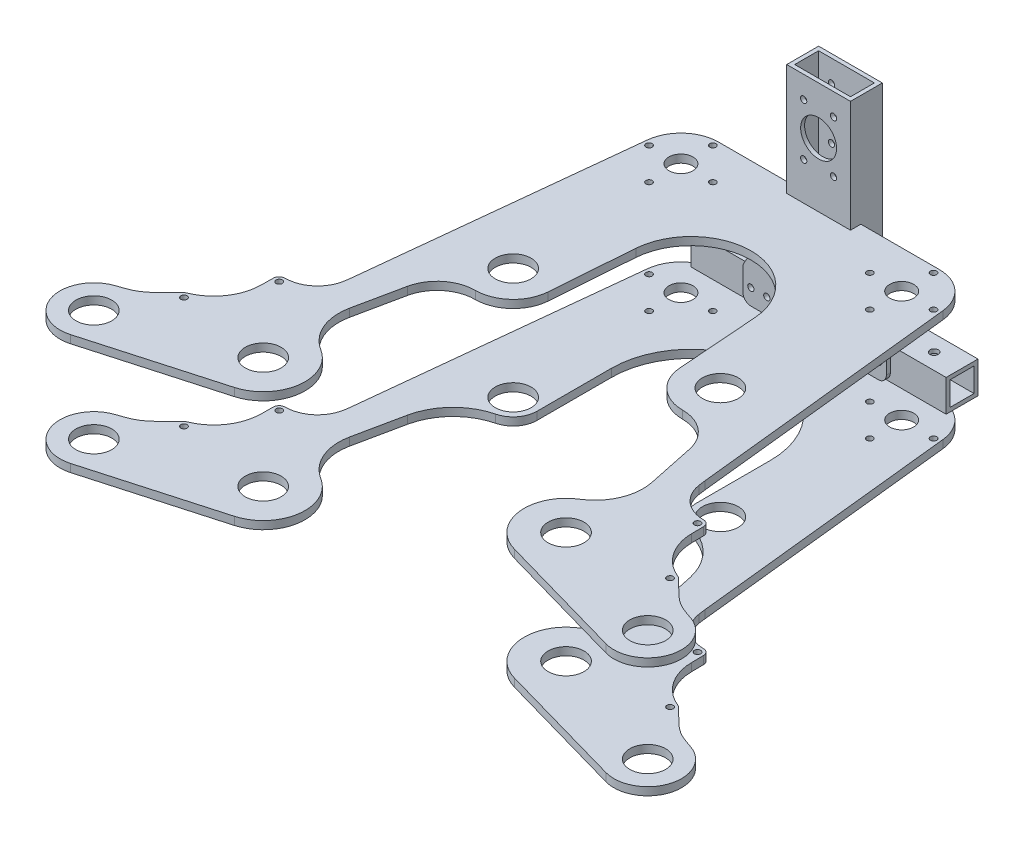
SolidWorks part; units mm, degrees
ref_plane "Alzado" through (0, 0, 0) normal (0, 0, 1) x (1, 0, 0)
ref_plane "Planta" through (0, 0, 0) normal (0, 1, 0) x (1, 0, 0)
ref_plane "Vista lateral" through (0, 0, 0) normal (1, 0, 0) x (0, 0, -1)
sketch "llantas" plane through (0, 0, 0) normal (0, 1, 0) x (1, 0, 0)
  line L0 (0, 221.5734) -> (0, 0) construction
  line L1 (-215.9, 0) -> (0, 0) construction
  circle A0 centre (-93.6625, 101.6) radius 50.8
  circle A1 centre (-215.9, 0) radius 38.1
  circle A2 centre (215.9, 0) radius 38.1
  circle A3 centre (93.6625, 101.6) radius 50.8
  dimension "D1" = 101.6
  dimension "D2" = 42.8625
  dimension "D3" = 177.8
  dimension "D4" = 76.2
  dimension "D5" = 101.6
sketch "cono" plane through (0, 0, 0) normal (1, 0, 0) x (0, 0, -1)
  line L0 (-76.2, 23.114) -> (-22.987, 324.358)
  line L1 (-22.987, 324.358) -> (22.987, 324.358)
  line L2 (0, 324.358) -> (0, 23.114) construction
  line L3 (76.2, 23.114) -> (-76.2, 23.114) construction
  line L4 (-76.2, 23.114) -> (-106.426, 23.114)
  line L5 (-106.426, 23.114) -> (-106.426, 0)
  line L6 (-106.426, 0) -> (106.426, 0)
  line L7 (0, 0) -> (0, 23.114)
  line L8 (-76.2, 23.114) -> (76.2, 23.114)
  line L9 (-80.283, 0) -> (80.283, 0)
  line L10 (221.5734, 0) -> (0, 0) construction
  line L11 (106.426, 23.114) -> (106.426, 0)
  line L12 (76.2, 23.114) -> (106.426, 23.114)
  line L13 (76.2, 23.114) -> (22.987, 324.358)
  line L14 (0, 220.8278) -> (41.275, 220.8278) construction
  dimension "D1" = 324.358
  dimension "D2" = 23.114
  dimension "D3" = 22.987
  dimension "D4" = 152.4
  dimension "D5" = 212.852
  dimension "D6" = 41.275
  dimension "D7" = 220.8278
sketch "Croquis4" plane through (0, 0, 0) normal (0, 1, 0) x (1, 0, 0)
  line L11 (0, 293.4478) -> (0, -300.8756) construction
  circle A36 centre (0, 179.087) radius 32.258
  dimension "D4" = 64.516
ref_plane "Plano1" through (0, 184.15, 0) normal (0, 1, 0) x (1, 0, 0)
sketch "Croquis11" plane through (0, 184.15, 0) normal (0, 1, 0) x (1, 0, 0)
  line L0 (0, -106.426) -> (0, 106.426) construction
  line L1 (-97.4367, 80.798) -> (-111.0577, -56.3986) construction
  line L2 (0, 0) -> (0, -47.7539) construction
  line L3 (-78.5329, 81.5298) -> (-54.3464, -54.2032) construction
  line L4 (-102.0644, -224.6803) -> (-63.9644, -63.6256) construction
  line L5 (-139.2356, -215.8869) -> (-101.1356, -54.8321) construction
  line L6 (0, 0) -> (-82.55, -59.2289) construction
  line L7 (0, 0) -> (0, -106.426) construction
  line L14 (-126.947, -202.253) -> (-226.9506, -237.178) construction
  line L15 (-114.353, -238.3143) -> (-214.3566, -273.2393) construction
  line L16 (0, 293.4478) -> (0, -300.8756) construction
  line L17 (-220.6536, -283.7836) -> (-120.65, -283.7836) construction
  circle A0 centre (0, 0) radius 47.7539 construction
  circle A1 centre (-82.55, -59.2289) radius 50.8
  circle A2 centre (-87.9341, 79.8546) radius 30
  arc A3 (-78.5329, 81.5298) -> (-97.4367, 80.798) centre (-87.9341, 79.8546) ccw construction
  arc A4 (-111.0577, -56.3986) -> (-54.3464, -54.2032) centre (-82.55, -59.2289) ccw construction
  arc A6 (-139.2356, -215.8869) -> (-102.0644, -224.6803) centre (-120.65, -220.2836) ccw construction
  arc A7 (-63.9644, -63.6256) -> (-101.1356, -54.8321) centre (-82.55, -59.2289) ccw construction
  circle A12 centre (-120.65, -220.2836) radius 50.8
  circle A13 centre (-220.6536, -255.2086) radius 28.575
  arc A14 (-226.9506, -237.178) -> (-214.3566, -273.2393) centre (-220.6536, -255.2086) ccw construction
  arc A15 (-114.353, -238.3143) -> (-139.2356, -215.8869) centre (-120.65, -220.2836) ccw construction
  point P19 (0, 0)
  dimension "D1" = 101.6
  dimension "D4" = 60
  dimension "D5" = 19.0986
  dimension "D6" = 57.2958
  dimension "D10" = 38.1972
  dimension "D17" = 101.6
  dimension "D13" = 57.15
  dimension "D14" = 38.1972
  dimension "D2" = 101.6
  dimension "D3" = 165.1
  dimension "D8" = 69.85
  dimension "D9" = 12.7
sketch "Croquis40" plane through (0, 184.15, 0) normal (0, 1, 0) x (1, 0, 0)
  line L0 (-117.475, -110.0289) -> (117.475, -110.0289) construction
  line L1 (-117.475, -110.0289) -> (-117.475, -344.9789) construction
  line L2 (117.475, -110.0289) -> (117.475, -344.9789) construction
  line L3 (-117.475, -344.9789) -> (117.475, -344.9789) construction
  line L4 (0, 0) -> (0, -110.0289)
  circle A1 centre (-82.55, -59.2289) radius 50.8 construction
  dimension "D1" = 234.95
ref_plane "Plano2" through (0, 95.25, 0) normal (0, 1, 0) x (1, 0, 0)
sketch "Croquis12" plane through (0, 95.25, 0) normal (0, 1, 0) x (1, 0, 0)
  line L0 (0, 0) -> (0, -63.4576) construction
  circle A0 centre (0, 0) radius 63.4576 construction
  circle A1 centre (-82.55, -59.2289) radius 50.8
  circle A2 centre (-82.55, -59.2289) radius 50.8 construction
sketch "Croquis42" plane through (0, 184.15, 0) normal (0, 1, 0) x (1, 0, 0)
  line L10 (140.3668, -129.3051) -> (117.7656, 83.0299)
  line L11 (-47.6217, 3.5515) -> (-52.471, -61.4721)
  line L12 (-112.3836, -113.6275) -> (-120.3575, -151.7275)
  line L13 (-120.65, -220.2836) -> (-220.6536, -255.2086) construction
  line L14 (-111.5648, -252.3593) -> (-213.299, -281.1746)
  line L15 (0, 226.6032) -> (0, -226.6032) construction
  line L17 (229.5516, -229.7302) -> (216.339, -225.1159)
  line L18 (-229.5516, -229.7302) -> (-216.339, -225.1159)
  line L19 (-140.3668, -129.3051) -> (-117.7656, 83.0299)
  line L20 (-126.947, -202.253) -> (-226.9506, -237.178) construction
  line L21 (-87.9341, 109.8546) -> (87.9341, 109.8546)
  line L22 (111.5648, -252.3593) -> (213.299, -281.1746)
  line L23 (112.3836, -113.6275) -> (120.3575, -151.7275)
  line L24 (47.6217, 3.5515) -> (52.471, -61.4721)
  circle A11 centre (-220.6536, -255.2086) radius 14.2875
  circle A17 centre (-120.65, -220.2836) radius 14.2875
  circle A18 centre (-82.55, -59.2289) radius 14.2875
  arc A20 (47.6217, 3.5515) -> (-47.6217, 3.5515) centre (0, 0) ccw
  circle A21 centre (87.9341, 79.8546) radius 25.4 construction
  circle A22 centre (0, 0) radius 47.7539 construction
  arc A23 (-82.55, -89.3914) -> (-52.471, -61.4721) centre (-82.55, -59.2289) ccw
  arc A24 (-82.55, -89.3914) -> (-112.3836, -113.6275) centre (-82.55, -119.8714) ccw
  arc A25 (-111.5648, -252.3593) -> (-103.1106, -191.933) centre (-120.65, -220.2836) ccw
  arc A26 (-120.3575, -151.7275) -> (-103.1106, -191.933) centre (-83.0655, -159.5323) ccw
  arc A28 (-229.5516, -229.7302) -> (-213.299, -281.1746) centre (-220.6536, -255.2086) ccw
  circle A29 centre (120.65, -220.2836) radius 33.3375 construction
  circle A30 centre (113.3341, 79.8546) radius 2.4892
  circle A31 centre (-87.9341, 79.8546) radius 30 construction
  arc A32 (-87.9341, 109.8546) -> (-117.7656, 83.0299) centre (-87.9341, 79.8546) ccw
  circle A33 centre (-120.65, -220.2836) radius 33.3375 construction
  circle A34 centre (-87.9341, 79.8546) radius 25.4 construction
  circle A35 centre (-87.9341, 105.2546) radius 2.4892
  circle A36 centre (-62.5341, 79.8546) radius 2.4892
  circle A37 centre (-87.9341, 54.4546) radius 2.4892
  circle A38 centre (-113.3341, 79.8546) radius 2.4892
  circle A39 centre (87.9341, 54.4546) radius 2.4892
  circle A40 centre (62.5341, 79.8546) radius 2.4892
  circle A41 centre (87.9341, 105.2546) radius 2.4892
  arc A42 (87.9341, 109.8546) -> (117.7656, 83.0299) centre (87.9341, 79.8546) cw
  arc A43 (229.5516, -229.7302) -> (213.299, -281.1746) centre (220.6536, -255.2086) cw
  arc A44 (120.3575, -151.7275) -> (103.1106, -191.933) centre (83.0655, -159.5323) cw
  arc A45 (111.5648, -252.3593) -> (103.1106, -191.933) centre (120.65, -220.2836) cw
  arc A46 (82.55, -89.3914) -> (112.3836, -113.6275) centre (82.55, -119.8714) cw
  arc A47 (82.55, -89.3914) -> (52.471, -61.4721) centre (82.55, -59.2289) cw
  circle A48 centre (82.55, -59.2289) radius 14.2875
  circle A49 centre (120.65, -220.2836) radius 14.2875
  circle A50 centre (220.6536, -255.2086) radius 14.2875
  arc A52 (140.3668, -129.3051) -> (216.339, -225.1159) centre (254.0248, -117.2072) ccw
  arc A53 (-216.339, -225.1159) -> (-140.3668, -129.3051) centre (-254.0248, -117.2072) ccw
  circle A54 centre (-87.9341, 79.8546) radius 9.5631
  circle A55 centre (87.9341, 79.8546) radius 9.5631
  point P18 (-170.6518, -237.7461)
  point P52 (-87.9341, 79.8546)
  point P66 (148.0256, -201.2583)
  point P83 (0, 109.8546)
  point P85 (87.9341, 79.8546)
  point P86 (170.6518, -237.7461)
  point P90 (-148.0256, -201.2583)
  dimension "D1" = 28.575
  dimension "D2" = 19.05
  dimension "D3" = 12.7
  dimension "D4" = 15.875
  dimension "D5" = 38.1
  dimension "D7" = 30.48
  dimension "D8" = 50.8
  dimension "D9" = 4.9784
  dimension "D11" = 114.3
  dimension "D12" = 19.1262
  dimension "D6" = 38.1
  dimension "D10" = 4
extrude "4400-23-P-0501" add sketch "Croquis42" along normal blind 6.35
sketch "Croquis44" plane through (0, 95.25, 0) normal (0, 1, 0) x (1, 0, 0)
  line L0 (87.9341, 109.8546) -> (-87.9341, 109.8546) construction
  line L1 (-117.7656, 83.0299) -> (-140.3668, -129.3051) construction
  line L2 (87.9341, 109.8546) -> (-87.9341, 109.8546)
  line L3 (-117.7656, 83.0299) -> (-140.3668, -129.3051)
  line L4 (140.3668, -129.3051) -> (117.7656, 83.0299) construction
  line L5 (229.5516, -229.7302) -> (216.339, -225.1159) construction
  line L6 (111.5648, -252.3593) -> (213.299, -281.1746) construction
  line L7 (112.3836, -113.6275) -> (120.3575, -151.7275) construction
  line L10 (-120.3575, -151.7275) -> (-112.3836, -113.6275) construction
  line L11 (-213.299, -281.1746) -> (-111.5648, -252.3593) construction
  line L12 (-216.339, -225.1159) -> (-229.5516, -229.7302) construction
  line L13 (140.3668, -129.3051) -> (117.7656, 83.0299)
  line L14 (229.5516, -229.7302) -> (216.339, -225.1159)
  line L15 (111.5648, -252.3593) -> (213.299, -281.1746)
  line L16 (112.3836, -113.6275) -> (120.3575, -151.7275)
  line L19 (-120.3575, -151.7275) -> (-112.3836, -113.6275)
  line L20 (-213.299, -281.1746) -> (-111.5648, -252.3593)
  line L21 (-216.339, -225.1159) -> (-229.5516, -229.7302)
  line L22 (-63.4576, -59.2289) -> (-63.4576, 0)
  line L23 (63.4576, -59.2289) -> (63.4576, 0)
  line L24 (0, 0) -> (0, -147.841) construction
  arc A0 (-216.339, -225.1159) -> (-140.3668, -129.3051) centre (-254.0248, -117.2072) ccw construction
  arc A1 (-87.9341, 109.8546) -> (-117.7656, 83.0299) centre (-87.9341, 79.8546) ccw construction
  arc A2 (-216.339, -225.1159) -> (-140.3668, -129.3051) centre (-254.0248, -117.2072) ccw
  arc A3 (-87.9341, 109.8546) -> (-117.7656, 83.0299) centre (-87.9341, 79.8546) ccw
  arc A4 (117.7656, 83.0299) -> (87.9341, 109.8546) centre (87.9341, 79.8546) ccw construction
  arc A5 (140.3668, -129.3051) -> (216.339, -225.1159) centre (254.0248, -117.2072) ccw construction
  arc A6 (213.299, -281.1746) -> (229.5516, -229.7302) centre (220.6536, -255.2086) ccw construction
  arc A7 (103.1106, -191.933) -> (111.5648, -252.3593) centre (120.65, -220.2836) ccw construction
  arc A8 (103.1106, -191.933) -> (120.3575, -151.7275) centre (83.0655, -159.5323) ccw construction
  arc A14 (-120.3575, -151.7275) -> (-103.1106, -191.933) centre (-83.0655, -159.5323) ccw construction
  arc A15 (-111.5648, -252.3593) -> (-103.1106, -191.933) centre (-120.65, -220.2836) ccw construction
  arc A16 (-229.5516, -229.7302) -> (-213.299, -281.1746) centre (-220.6536, -255.2086) ccw construction
  arc A17 (117.7656, 83.0299) -> (87.9341, 109.8546) centre (87.9341, 79.8546) ccw
  arc A18 (140.3668, -129.3051) -> (216.339, -225.1159) centre (254.0248, -117.2072) ccw
  arc A19 (213.299, -281.1746) -> (229.5516, -229.7302) centre (220.6536, -255.2086) ccw
  arc A20 (103.1106, -191.933) -> (111.5648, -252.3593) centre (120.65, -220.2836) ccw
  arc A21 (103.1106, -191.933) -> (120.3575, -151.7275) centre (83.0655, -159.5323) ccw
  arc A27 (-120.3575, -151.7275) -> (-103.1106, -191.933) centre (-83.0655, -159.5323) ccw
  arc A28 (-111.5648, -252.3593) -> (-103.1106, -191.933) centre (-120.65, -220.2836) ccw
  arc A29 (-229.5516, -229.7302) -> (-213.299, -281.1746) centre (-220.6536, -255.2086) ccw
  circle A30 centre (87.9341, 79.8546) radius 9.5631 construction
  circle A31 centre (87.9341, 54.4546) radius 2.4892 construction
  circle A32 centre (113.3341, 79.8546) radius 2.4892 construction
  circle A33 centre (87.9341, 105.2546) radius 2.4892 construction
  circle A34 centre (62.5341, 79.8546) radius 2.4892 construction
  circle A35 centre (-87.9341, 79.8546) radius 9.5631 construction
  circle A36 centre (-62.5341, 79.8546) radius 2.4892 construction
  circle A37 centre (-87.9341, 105.2546) radius 2.4892 construction
  circle A38 centre (-113.3341, 79.8546) radius 2.4892 construction
  circle A39 centre (-87.9341, 54.4546) radius 2.4892 construction
  circle A40 centre (220.6536, -255.2086) radius 14.2875 construction
  circle A41 centre (120.65, -220.2836) radius 14.2875 construction
  circle A42 centre (82.55, -59.2289) radius 14.2875 construction
  circle A43 centre (-82.55, -59.2289) radius 14.2875 construction
  circle A44 centre (-120.65, -220.2836) radius 14.2875 construction
  circle A45 centre (-220.6536, -255.2086) radius 14.2875 construction
  circle A46 centre (87.9341, 79.8546) radius 9.5631
  circle A47 centre (87.9341, 54.4546) radius 2.4892
  circle A48 centre (113.3341, 79.8546) radius 2.4892
  circle A49 centre (87.9341, 105.2546) radius 2.4892
  circle A50 centre (62.5341, 79.8546) radius 2.4892
  circle A51 centre (-87.9341, 79.8546) radius 9.5631
  circle A52 centre (-62.5341, 79.8546) radius 2.4892
  circle A53 centre (-87.9341, 105.2546) radius 2.4892
  circle A54 centre (-113.3341, 79.8546) radius 2.4892
  circle A55 centre (-87.9341, 54.4546) radius 2.4892
  circle A56 centre (220.6536, -255.2086) radius 14.2875
  circle A57 centre (120.65, -220.2836) radius 14.2875
  circle A58 centre (82.55, -59.2289) radius 14.2875
  circle A59 centre (-82.55, -59.2289) radius 14.2875
  circle A60 centre (-120.65, -220.2836) radius 14.2875
  circle A61 centre (-220.6536, -255.2086) radius 14.2875
  arc A62 (63.4576, 0) -> (-63.4576, 0) centre (0, 0) ccw
  arc A64 (-63.4576, -59.2289) -> (-77.9, -77.7463) centre (-82.55, -59.2289) cw
  arc A65 (-112.3836, -113.6275) -> (-77.9, -77.7463) centre (-66.477, -123.2353) cw
  circle A66 centre (0, 0) radius 63.4576 construction
  arc A67 (112.3836, -113.6275) -> (77.9, -77.7463) centre (66.477, -123.2353) ccw
  arc A68 (63.4576, -59.2289) -> (77.9, -77.7463) centre (82.55, -59.2289) ccw
extrude "4400-23-P-0502" add sketch "Croquis44" along normal blind 6.35
sketch "Croquis45" plane through (0, 95.25, 0) normal (0, -1, 0) x (1, 0, 0)
  line L7 (-126.947, 202.253) -> (-226.9506, 237.178) construction
  circle A0 centre (-189.6273, 213.7178) radius 4.7625 construction
  circle A1 centre (-189.6273, 213.7178) radius 2.4892
  circle A6 centre (-220.6536, 255.2086) radius 38.1
  circle A7 centre (-220.6536, 255.2086) radius 38.1 construction
  circle A9 centre (-120.65, 220.2836) radius 63.5
  circle A10 centre (-120.65, 220.2836) radius 63.5 construction
  dimension "D1" = 9.525
  dimension "D2" = 4.9784
  dimension "D5" = 5.08
  dimension "D3" = 9.525
  dimension "D4" = 12.7
sketch "Croquis46" plane through (0, 190.5, 0) normal (0, 1, 0) x (1, 0, 0)
  line L0 (-184.6841, -242.6467) -> (-180.5992, -241.2201) construction
  line L1 (-126.947, -202.253) -> (-226.9506, -237.178) construction
  line L2 (-220.6536, -255.2086) -> (-120.65, -220.2836) construction
  line L3 (-182.6417, -241.9334) -> (-193.6494, -210.4142) construction
  line L4 (-166.6601, -156.7836) -> (-120.65, -156.7836) construction
  line L5 (-215.1814, -224.7046) -> (-196.9691, -206.9994)
  line L6 (-171.8045, -196.6069) -> (-195.4084, -205.9885)
  line L7 (-171.8045, -196.6069) -> (-171.4223, -161.4943)
  line L8 (0, 0) -> (0, -195.4432) construction
  line L9 (166.6601, -156.7836) -> (120.65, -156.7836) construction
  line L10 (182.6417, -241.9334) -> (193.6494, -210.4142) construction
  line L11 (220.6536, -255.2086) -> (120.65, -220.2836) construction
  line L12 (184.6841, -242.6467) -> (180.5992, -241.2201) construction
  line L13 (171.8045, -196.6069) -> (171.4223, -161.4943)
  line L14 (171.8045, -196.6069) -> (195.4084, -205.9885)
  line L15 (215.1814, -224.7046) -> (196.9691, -206.9994)
  circle A0 centre (-220.6536, -255.2086) radius 38.1 construction
  circle A1 centre (-193.6494, -210.4142) radius 4.7625 construction
  circle A2 centre (-193.6494, -210.4142) radius 2.4892
  circle A3 centre (-166.6601, -161.5461) radius 4.7625 construction
  circle A4 centre (-166.6601, -161.5461) radius 2.4892
  arc A5 (-216.339, -225.1159) -> (-140.3668, -129.3051) centre (-254.0248, -117.2072) ccw construction
  circle A6 centre (-120.65, -220.2836) radius 63.5 construction
  arc A7 (-196.9691, -206.9994) -> (-195.4084, -205.9885) centre (-193.6494, -210.4142) cw
  arc A8 (-171.4223, -161.4943) -> (-166.6601, -156.7836) centre (-166.6601, -161.5461) cw
  arc A9 (-166.6601, -156.7836) -> (-141.1068, -134.9277) centre (-166.6601, -130.9175) ccw
  arc A10 (-215.1814, -224.7046) -> (-141.1068, -134.9277) centre (-254.0248, -117.2072) ccw
  circle A11 centre (166.6601, -161.5461) radius 4.7625 construction
  circle A12 centre (193.6494, -210.4142) radius 4.7625 construction
  arc A13 (215.1814, -224.7046) -> (141.1068, -134.9277) centre (254.0248, -117.2072) cw
  arc A14 (166.6601, -156.7836) -> (141.1068, -134.9277) centre (166.6601, -130.9175) cw
  arc A15 (171.4223, -161.4943) -> (166.6601, -156.7836) centre (166.6601, -161.5461) ccw
  arc A16 (196.9691, -206.9994) -> (195.4084, -205.9885) centre (193.6494, -210.4142) ccw
  circle A17 centre (166.6601, -161.5461) radius 2.4892
  circle A18 centre (193.6494, -210.4142) radius 2.4892
  point P20 (-182.6417, -241.9334)
  arc M29 (216.339, -225.1159) -> (140.3668, -129.3051) centre (254.0248, -117.2072) cw
  arc M35 (-140.3668, -129.3051) -> (-216.339, -225.1159) centre (-254.0248, -117.2072) cw
  dimension "D1" = 4.9784
  dimension "D2" = 9.525
  dimension "D4" = 6.35
  dimension "D3" = 9.525
  dimension "D5" = 25.4
extrude "Saliente-Extruir2" add sketch "Croquis46" against normal up to surface (6.35 mm away) contours A9 A8 L7 A4 M35 | A7 L5 A2 L6 M35 | L13 A15 A14 A17 M29 | A18 L15 A16 L14 M29 region at (-160.7365, 190.5, 168.9261) region at (-205.715, 190.5, 216.2225) region at (160.7365, 190.5, 168.9261) region at (183.4155, 190.5, 201.778) up to face at (0, 184.15, 117.4282)
fillet "Redondeo1" radius 38.1 2 edges at (-215.1814, 187.325, 224.7046) (-171.8045, 187.325, 196.6069)
extrude "Saliente-Extruir3" add sketch "Croquis46<3>" against normal up to surface (95.25 mm away) from surface contours A9 A8 L7 A4 M35 | A7 L5 A2 L6 M35 | L13 A15 A14 A17 M29 | A18 L15 A16 L14 M29 region at (-160.7365, 190.5, 168.9261) region at (-205.715, 190.5, 216.2225) region at (160.7365, 190.5, 168.9261) region at (183.4155, 190.5, 201.778) up to face at (0, 95.25, 115.6558) starting at face at (-120.65, 101.6, 234.5711)
sketch "Croquis46<3>" plane through (0, 190.5, 0) normal (0, 1, 0) x (1, 0, 0) same geometry as "Croquis46"
fillet "Redondeo2" radius 38.1 2 edges at (-215.1814, 98.425, 224.7046) (-171.8045, 98.425, 196.6069)
fillet "Redondeo3" radius 38.1 2 edges at (215.1814, 187.325, 224.7046) (171.8045, 187.325, 196.6069)
fillet "Redondeo4" radius 38.1 2 edges at (215.1814, 98.425, 224.7046) (171.8045, 98.425, 196.6069)
sketch "Croquis47" plane through (0, 190.5, 0) normal (0, 1, 0) x (1, 0, 0)
  line L0 (-139.2356, -215.8869) -> (-101.1356, -54.8321) construction
  line L4 (0, 0) -> (0, -211.1114) construction
  line L9 (-97.4367, 80.798) -> (-111.0577, -56.3986) construction
  line L12 (87.9341, 109.8546) -> (-87.9341, 109.8546) construction
  line L14 (-78.5329, 81.5298) -> (-54.3464, -54.2032) construction
  circle A0 centre (-136.2788, -144.0836) radius 4.7625 construction
  circle A1 centre (-136.2788, -144.0836) radius 2.4892
  circle A2 centre (-130.8514, -121.1414) radius 4.7625 construction
  circle A3 centre (-130.8514, -121.1414) radius 2.4892
  circle A5 centre (-120.65, -220.2836) radius 63.5 construction
  circle A7 centre (-82.55, -59.2289) radius 50.8 construction
  circle A8 centre (130.8514, -121.1414) radius 2.4892
  circle A9 centre (130.8514, -121.1414) radius 4.7625 construction
  circle A10 centre (136.2788, -144.0836) radius 2.4892
  circle A11 centre (136.2788, -144.0836) radius 4.7625 construction
  circle A12 centre (-118.4992, 19.6921) radius 2.4892
  circle A13 centre (-118.4992, 19.6921) radius 4.7625 construction
  circle A14 centre (-121.3218, 16.9711) radius 2.4892
  circle A15 centre (-121.3218, 16.9711) radius 4.7625 construction
  circle A17 centre (-87.9341, 79.8546) radius 30 construction
  circle A18 centre (121.3218, 16.9711) radius 4.7625 construction
  circle A19 centre (121.3218, 16.9711) radius 2.4892
  circle A20 centre (118.4992, 19.6921) radius 4.7625 construction
  circle A21 centre (118.4992, 19.6921) radius 2.4892
  circle A22 centre (-44.2816, 98.7421) radius 4.7625 construction
  circle A23 centre (-44.2816, 98.7421) radius 2.4892
  circle A24 centre (44.2816, 98.7421) radius 2.4892
  circle A25 centre (44.2816, 98.7421) radius 4.7625 construction
  circle A26 centre (-7.1562, 80.603) radius 4.7625 construction
  circle A27 centre (-7.1562, 80.603) radius 2.4892
  circle A28 centre (-38.6142, 65.6424) radius 2.4892
  circle A29 centre (-38.6142, 65.6424) radius 4.7625 construction
  circle A31 centre (0, 0) radius 63.4576 construction
  circle A32 centre (38.6142, 65.6424) radius 2.4892
  circle A33 centre (38.6142, 65.6424) radius 4.7625 construction
  dimension "D1" = 4.9784
  dimension "D2" = 9.525
  dimension "D3" = 8.89
  dimension "D4" = 8.89
  dimension "D5" = 12.7
  dimension "D6" = 6.35
  dimension "D7" = 9.525
  dimension "D8" = 4.9784
  dimension "D9" = 12.7
  dimension "D10" = 10.16
  dimension "D11" = 25.4
  dimension "D12" = 25.4
  dimension "D13" = 4.9784
  dimension "D14" = 9.525
  dimension "D15" = 8.89
  dimension "D16" = 6.35
  dimension "D17" = 9.525
  dimension "D18" = 4.9784
  dimension "D19" = 12.7
  dimension "D20" = 65.3447
  dimension "D21" = 12.7
  dimension "D22" = 31.75
extrude "Cortar-Extruir1" cut sketch "Croquis47" against normal through all rebuild error yes
sketch "Croquis48" plane through (0, 101.6, 0) normal (0, 1, 0) x (1, 0, 0)
  line L1 (-101.6, 127) -> (101.6, 127)
  line L2 (-101.6, 127) -> (-101.6, 101.6)
  line L3 (-101.6, 101.6) -> (101.6, 101.6)
  line L4 (101.6, 127) -> (101.6, 101.6)
  line L5 (-101.6, 127) -> (101.6, 101.6) construction
  line L6 (-101.6, 101.6) -> (101.6, 127) construction
  point P0 (0, 114.3)
  dimension "D1" = 25.4
  dimension "D2" = 203.2
  dimension "D3" = 114.3
extrude "Saliente-Extruir4" add sketch "Croquis48" along normal blind 25.4 from surface separate body starting at face at (-120.65, 101.6, 234.5711)
shell "Vaciado1" thickness 3.175 removed face at (-101.6, 114.3, -114.3) removed face at (101.6, 114.3, -114.3)
sketch "Croquis49" plane through (0, 127, 0) normal (0, 1, 0) x (1, 0, 0)
  line L0 (0, 127) -> (0, 101.6) construction
  line L1 (-101.6, 127) -> (101.6, 127) construction
  line L2 (101.6, 101.6) -> (-101.6, 101.6) construction
  line L3 (-101.6, 114.3) -> (0, 114.3) construction
  line L4 (-101.6, 101.6) -> (-101.6, 127) construction
  line L6 (-25.4, 101.6) -> (25.4, 101.6)
  line L7 (-25.4, 101.6) -> (-25.4, 127)
  line L8 (-25.4, 127) -> (25.4, 127)
  line L9 (25.4, 101.6) -> (25.4, 127)
  line L10 (-25.4, 101.6) -> (25.4, 127) construction
  line L11 (-25.4, 127) -> (25.4, 101.6) construction
  dimension "D1" = 50.8
extrude "Saliente-Extruir5" add sketch "Croquis49" along normal blind 152.4 separate body
shell "Vaciado2" thickness 3.175 removed face at (0, 279.4, -114.3) removed face at (0, 127, -114.3)
sketch "Croquis50" plane through (0, 0, -101.6) normal (0, 0, 1) x (1, 0, 0)
  line L0 (-47.6217, 184.15) -> (47.6217, 184.15) construction
  line L1 (0, 241.2619) -> (11.9062, 261.8841) construction
  line L2 (-25.4, 279.4) -> (25.4, 279.4) construction
  line L3 (0, 241.2619) -> (0, 279.4) construction
  circle A0 centre (0, 241.2619) radius 14.3129
  circle A1 centre (0, 241.2619) radius 23.8125 construction
  circle A2 centre (11.9062, 261.8841) radius 2.4892
  circle A3 centre (23.8125, 241.2619) radius 2.4892 construction
  circle A4 centre (11.9062, 220.6397) radius 2.4892
  circle A5 centre (-11.9063, 220.6397) radius 2.4892
  circle A6 centre (-23.8125, 241.2619) radius 2.4892 construction
  circle A7 centre (-11.9063, 261.8841) radius 2.4892
  dimension "D1" = 57.1119
  dimension "D2" = 28.6258
  dimension "D3" = 47.625
  dimension "D4" = 4.9784
  dimension "D6" = 23.8125
  dimension "D5" = 6
extrude "Cortar-Extruir2" cut sketch "Croquis50" against normal through all
sketch "Croquis53" plane through (0, 0, -101.6) normal (0, 0, 1) x (1, 0, 0)
  line L0 (-101.6, 114.3) -> (101.6, 114.3) construction
  line L1 (-101.6, 127) -> (-101.6, 101.6) construction
  line L2 (101.6, 127) -> (101.6, 101.6) construction
  line L3 (0, 114.3) -> (12.7, 114.3) construction
  line L4 (0, 114.3) -> (0, 279.4) construction
  line L5 (-25.4, 279.4) -> (25.4, 279.4) construction
  line L6 (-12.7, 114.3) -> (-12.7, 127) construction
  line L7 (50.8, 101.6) -> (-50.8, 101.6)
  line L9 (101.6, 101.6) -> (-101.6, 101.6) construction
  line L10 (-57.15, 107.95) -> (-57.15, 125.3481)
  line L11 (101.6, 127) -> (-101.6, 127) construction
  line L12 (-56.3451, 128.4425) -> (-27.2168, 180.6403)
  line L13 (-25.4, 279.4) -> (-25.4, 127) construction
  line L14 (-21.6717, 183.896) -> (21.6717, 183.896)
  line L15 (57.15, 107.95) -> (57.15, 125.3481)
  line L16 (56.3451, 128.4425) -> (27.2168, 180.6403)
  circle A0 centre (0, 114.3) radius 2.4892
  circle A1 centre (12.7, 114.3) radius 2.4892
  circle A2 centre (25.4, 114.3) radius 2.4892
  circle A3 centre (38.1, 114.3) radius 2.4892
  circle A4 centre (50.8, 114.3) radius 2.4892
  circle A5 centre (-50.8, 114.3) radius 2.4892
  circle A6 centre (-38.1, 114.3) radius 2.4892
  circle A7 centre (-25.4, 114.3) radius 2.4892
  circle A8 centre (-12.7, 114.3) radius 2.4892
  circle A10 centre (-12.7, 127) radius 2.4892 [skipped]
  circle A11 centre (12.7, 127) radius 2.4892 [skipped]
  circle A12 centre (-12.7, 139.7) radius 2.4892
  circle A13 centre (12.7, 139.7) radius 2.4892
  circle A14 centre (-12.7, 152.4) radius 2.4892
  circle A15 centre (12.7, 152.4) radius 2.4892
  circle A16 centre (-12.7, 165.1) radius 2.4892
  circle A17 centre (12.7, 165.1) radius 2.4892
  circle A18 centre (-12.7, 177.8) radius 2.4892
  circle A19 centre (12.7, 177.8) radius 2.4892
  arc A20 (57.15, 107.95) -> (50.8, 101.6) centre (50.8, 107.95) cw
  arc A21 (57.15, 125.3481) -> (56.3451, 128.4425) centre (50.8, 125.3481) ccw
  arc A22 (27.2168, 180.6403) -> (21.6717, 183.896) centre (21.6717, 177.546) ccw
  arc A23 (-27.2168, 180.6403) -> (-21.6717, 183.896) centre (-21.6717, 177.546) cw
  arc A24 (-57.15, 125.3481) -> (-56.3451, 128.4425) centre (-50.8, 125.3481) cw
  arc A25 (-50.8, 101.6) -> (-57.15, 107.95) centre (-50.8, 107.95) cw
  point P63 (0, 101.6)
  point P65 (0, 183.896)
  point P68 (57.15, 101.6)
  point P71 (57.15, 127)
  point P74 (25.4, 183.896)
  point P77 (-25.4, 183.896)
  point P80 (-57.15, 127)
  point P83 (-57.15, 101.6)
  dimension "D1" = 4.9784
  dimension "D4" = 6
  dimension "D8" = 6.35
  dimension "D3" = 12.7
  dimension "D5" = 12.7
  dimension "D6" = 6.096
  dimension "D7" = 6.35
  dimension "D2" = 5
extrude "Saliente-Extruir6" add sketch "Croquis53" along normal blind 3.175 separate body
sketch "Croquis55" plane through (0, 0, -98.425) normal (0, 0, 1) x (1, 0, 0)
  circle A0 centre (-12.7, 114.3) radius 2.4892 construction
  circle A1 centre (-12.7, 139.7) radius 2.4892 construction
  circle A2 centre (-25.4, 114.3) radius 2.4892 construction
  circle A3 centre (-38.1, 114.3) radius 2.4892 construction
  circle A4 centre (-50.8, 114.3) radius 2.4892 construction
  circle A5 centre (-12.7, 114.3) radius 2.4892
  circle A6 centre (-12.7, 139.7) radius 2.4892
  circle A7 centre (-25.4, 114.3) radius 2.4892
  circle A8 centre (-38.1, 114.3) radius 2.4892
  circle A9 centre (-50.8, 114.3) radius 2.4892
  circle A10 centre (-12.7, 165.1) radius 2.4892 construction
  circle A11 centre (-12.7, 152.4) radius 2.4892 construction
  circle A12 centre (-12.7, 165.1) radius 2.4892
  circle A13 centre (-12.7, 152.4) radius 2.4892
  circle A14 centre (-12.7, 177.8) radius 2.4892 construction
  circle A15 centre (-12.7, 177.8) radius 2.4892
  circle A16 centre (12.7, 165.1) radius 2.4892 construction
  circle A17 centre (12.7, 177.8) radius 2.4892 construction
  circle A18 centre (12.7, 165.1) radius 2.4892
  circle A19 centre (12.7, 177.8) radius 2.4892
  circle A20 centre (0, 114.3) radius 2.4892 construction
  circle A21 centre (12.7, 114.3) radius 2.4892 construction
  circle A22 centre (12.7, 139.7) radius 2.4892 construction
  circle A23 centre (12.7, 152.4) radius 2.4892 construction
  circle A24 centre (0, 114.3) radius 2.4892
  circle A25 centre (12.7, 114.3) radius 2.4892
  circle A26 centre (12.7, 139.7) radius 2.4892
  circle A27 centre (12.7, 152.4) radius 2.4892
  circle A28 centre (50.8, 114.3) radius 2.4892 construction
  circle A29 centre (38.1, 114.3) radius 2.4892 construction
  circle A30 centre (25.4, 114.3) radius 2.4892 construction
  circle A31 centre (50.8, 114.3) radius 2.4892
  circle A32 centre (38.1, 114.3) radius 2.4892
  circle A33 centre (25.4, 114.3) radius 2.4892
extrude "Cortar-Extruir3" cut sketch "Croquis55" against normal up to surface (28.575 mm away) up to face at (-9.417, 261.8841, -127)
sketch "Croquis56" plane through (0, 101.6, 0) normal (0, -1, 0) x (1, 0, 0)
  line L0 (0, -101.6) -> (0, -127) construction
  line L1 (101.6, -101.6) -> (-101.6, -101.6) construction
  line L2 (-101.6, -127) -> (101.6, -127) construction
  line L3 (0, -114.3) -> (-101.6, -114.3) construction
  line L4 (-101.6, -101.6) -> (-101.6, -127) construction
  line L5 (-25.4, -114.3) -> (-25.4, -127) construction
  circle A0 centre (-47.625, -114.3) radius 3.2639
  circle A1 centre (-79.375, -114.3) radius 3.2639
  circle A2 centre (79.375, -114.3) radius 3.2639
  circle A3 centre (47.625, -114.3) radius 3.2639
  dimension "D1" = 25.4
  dimension "D2" = 6.5278
  dimension "D3" = 31.75
  dimension "D4" = 22.225
extrude "Cortar-Extruir4" cut sketch "Croquis56" against normal up to surface (25.4 mm away) up to face at (0, 127, -114.3)
sketch "Croquis57" plane through (0, 190.5, 0) normal (0, 1, 0) x (1, 0, 0)
  line L5 (0, 123.825) -> (0, 104.775) construction
  line L6 (22.225, 123.825) -> (-22.225, 123.825) construction
  line L7 (-22.225, 104.775) -> (22.225, 104.775) construction
  line L9 (-25.4381, 101.5619) -> (25.4381, 101.5619)
  line L10 (-25.4381, 101.5619) -> (-25.4381, 127.0381)
  line L11 (-25.4381, 127.0381) -> (25.4381, 127.0381)
  line L12 (25.4381, 101.5619) -> (25.4381, 127.0381)
  line L13 (-25.4381, 101.5619) -> (25.4381, 127.0381) construction
  line L14 (-25.4381, 127.0381) -> (25.4381, 101.5619) construction
  point P6 (0, 114.3)
  dimension "D1" = 25.4762
  dimension "D2" = 50.8762
extrude "Cortar-Extruir5" cut sketch "Croquis57" against normal up to next (63.5 mm away)
equation "\"D5@Croquis11\"=12*5MM/PI"
equation "\"D6@Croquis11\"=36*5mm/pi"
equation "\"D7@Croquis11\"=(80*5mm)+1mm"
equation "\"D10@Croquis11\"=24*5mm/pi"
equation "\"D11@Croquis11\"=(90*5mm)+1mm"
equation "\"D14@Croquis11\"=24*5mm/pi"
equation "\"D15@Croquis11\"=(70*5mm)+1mm"
